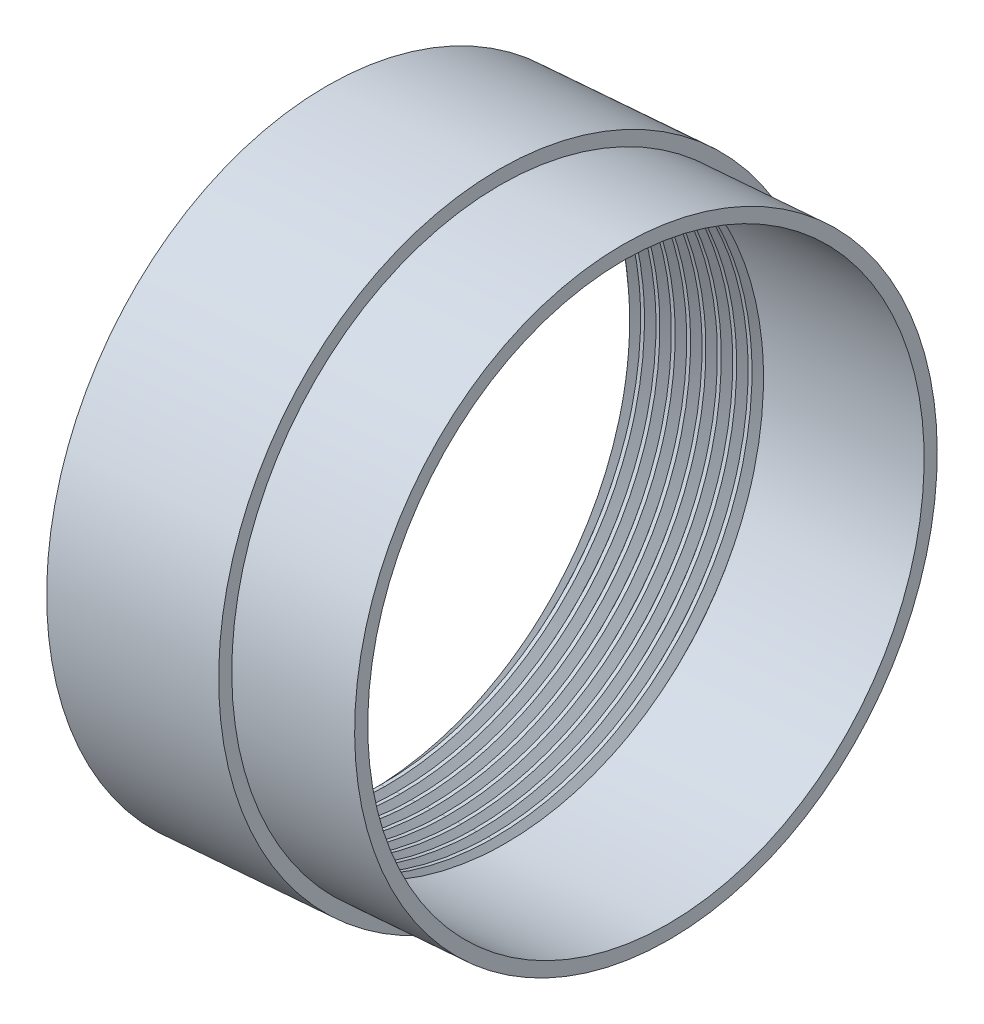
SolidWorks part; units mm, degrees
ref_plane "Front Plane" through (0, 0, 0) normal (0, 0, 1) x (1, 0, 0)
ref_plane "Top Plane" through (0, 0, 0) normal (0, 1, 0) x (1, 0, 0)
ref_plane "Right Plane" through (0, 0, 0) normal (1, 0, 0) x (0, 0, -1)
sketch "Sketch3" plane through (-310.5359, -24.7684, 0) normal (-0.9968, -0.0795, 0) x (0, 0, 1)
  circle A4 centre (43.1743, 14.6524) radius 14.9605
  circle A6 centre (43.1743, 14.6524) radius 14.2875
  dimension "D1" = 29.921
  dimension "D2" = 28.575
extrude "Boss-Extrude3" add sketch "Sketch3" against normal blind 6.35
sketch "Sketch4" plane through (-310.5359, -24.7684, 0) normal (-0.9968, -0.0795, 0) x (0, 0, 1)
  circle A1 centre (43.1743, 14.6524) radius 15.6337
  circle A3 centre (43.1743, 14.6524) radius 14.2875
  dimension "D1" = 31.2674
  dimension "D2" = 28.575
extrude "Boss-Extrude4" add sketch "Sketch4" along normal blind 8.89
thread "Thread1" pitch 0.7937 method cut profile "Thread Profile1" start angle 0, offset 0.7937, length 7.62, pitch 0.7937, diameter 28.575
ref_plane "Plane1" through (-321.3539, -10.9323, 28.8868) normal (0.0795, -0.9968, 0) x (0, 0, -1)
sketch "Thread Profile1" plane through (-321.3539, -10.9323, 28.8868) normal (0.0795, -0.9968, 0) x (0, 0, -1)
  line L0 (0, 0) -> (0, 0.7937) construction
  line L1 (0, 0) -> (0.4296, 0.248)
  line L2 (0.4296, 0.248) -> (0.4296, 0.3473)
  line L3 (0.4296, 0.3473) -> (0, 0.5953)
  line L4 (0.4296, 0.2977) -> (0, 0.2977) construction
  line L11 (0, 0) -> (0, 0.5953)
  point P2 (0, 0)
  dimension "Pitch" = 0.7937
  dimension "Profile_Angle" = 60
  dimension "Profile_Land" = 0.0992
  dimension "Profile_Height" = 0.4296
sketch "Sketch8" plane through (-319.3977, -25.4752, 0) normal (-0.9968, -0.0795, 0) x (0, 0, 1)
  arc A0 (48.8063, 1.0555) -> (56.7711, 9.0204) centre (43.1743, 14.6524) ccw construction
  arc A1 (48.8063, 1.0555) -> (56.7711, 9.0204) centre (43.1743, 14.6524) ccw
  dimension "D1" = 14.7171
